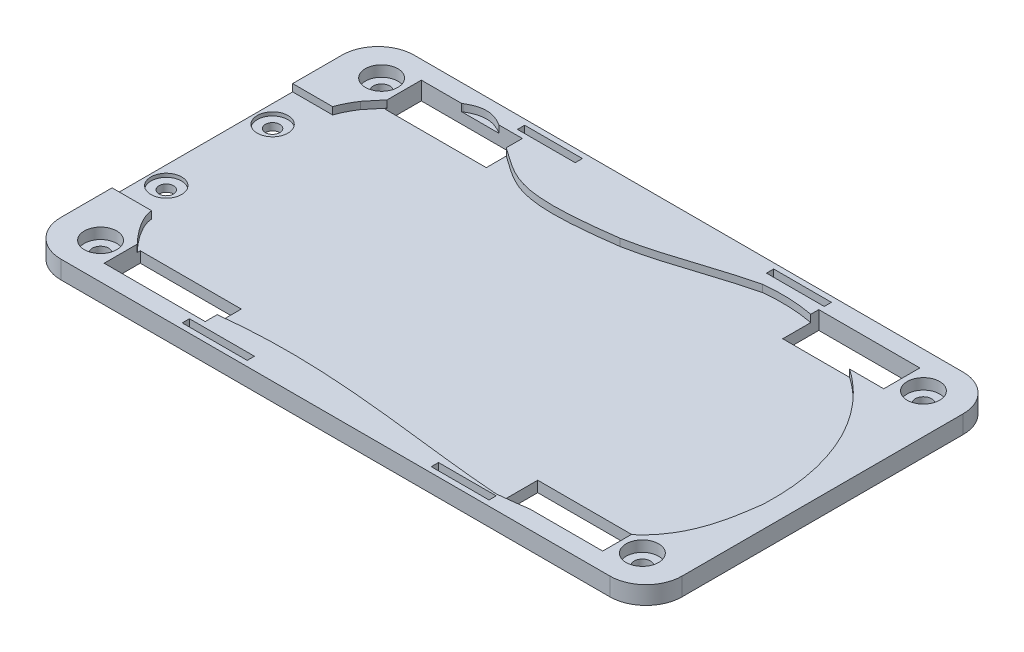
SolidWorks part; units mm, degrees
ref_plane "Front Plane" through (0, 0, 0) normal (0, 0, 1) x (1, 0, 0)
ref_plane "Top Plane" through (0, 0, 0) normal (0, 1, 0) x (1, 0, 0)
ref_plane "Right Plane" through (0, 0, 0) normal (1, 0, 0) x (0, 0, -1)
sketch "Sketch1" plane through (0, 0, 0) normal (0, 1, 0) x (1, 0, 0)
  line L1 (-78.1571, 35.933) -> (-78.1571, -14.1122)
  line L2 (78.9797, 0.0343) -> (-78.1571, 0.0343) construction
  line L3 (-77.1571, 35.7646) -> (-77.1571, -14.1122)
  line L4 (78.9797, -0.9657) -> (-78.1571, -0.9657)
  arc A1 (37.8695, -35.2975) -> (39.5975, -35.2134) centre (38.2635, -25.6055) ccw
  arc A2 (37.9263, -34.299) -> (39.4753, -34.2207) centre (38.2635, -25.6055) ccw
  spline S0 degree 1 poles (-77.1571, -14.1122) (-56.919, -31.9168) knots 0 0 1 1 construction
  spline S1 degree 1 poles (-56.919, -31.9168) (37.9263, -34.299) knots 0 0 1 1 construction
  spline S2 degree 1 poles (39.4753, -34.2207) (77.9849, 0.1477) knots 0 0 1 1 construction
  spline S3 degree 1 poles (77.9849, 0.1477) (25.0602, 52.8732) knots 0 0 1 1 construction
  spline S4 degree 1 poles (25.0602, 52.8732) (-5.6593, 44.1904) knots 0 0 1 1 construction
  spline S5 degree 1 poles (-5.6593, 44.1904) (-43.9853, 50.6886) knots 0 0 1 1 construction
  spline S6 degree 1 poles (-43.9853, 50.6886) (-59.7702, 54.7238) knots 0 0 1 1 construction
  spline S7 degree 1 poles (-59.7702, 54.7238) (-74.5158, 41.0521) knots 0 0 1 1 construction
  spline S8 degree 1 poles (-74.5158, 41.0521) (-77.1571, 35.7646) knots 0 0 1 1 construction
  spline S9 degree 3 poles (-77.1571, -14.1122) (-77.1565, -14.3701) (-77.1092, -14.8732) (-76.8359, -15.9559) (-76.1879, -17.5008) (-75.044, -19.4183) (-73.152, -22.0092) (-70.3495, -25.0822) (-66.8736, -28.0972) (-63.6864, -30.2141) (-61.0019, -31.4062) (-58.8274, -31.848) (-57.5718, -31.8794) (-56.919, -31.9168) knots 0.000484 0.000484 0.000484 0.000484 0.031521 0.062558 0.124632 0.186706 0.248781 0.372929 0.497077 0.621225 0.745373 0.869521 0.993669 0.993669 0.993669 0.993669
  spline S10 degree 3 poles (-56.919, -31.9168) (-56.6769, -31.8873) (-56.2021, -31.8274) (-55.1791, -31.687) (-53.8294, -31.4877) (-52.0759, -31.2184) (-49.5744, -30.8354) (-46.1465, -30.3372) (-41.5825, -29.7813) (-36.5976, -29.3261) (-29.4274, -28.913) (-19.5571, -28.8468) (-6.4839, -29.5875) (5.2448, -30.7865) (15.023, -31.9295) (22.521, -32.809) (30.1538, -33.642) (35.3408, -34.1075) (37.9263, -34.299) knots 0.000538 0.000538 0.000538 0.000538 0.016152 0.031766 0.062993 0.094221 0.125449 0.187904 0.250359 0.312815 0.37527 0.50018 0.625091 0.750001 0.812457 0.874912 0.937367 0.999822 0.999822 0.999822 0.999822
  spline S11 degree 3 poles (39.4753, -34.2207) (41.0079, -34.0574) (44.09, -33.7147) (50.0835, -32.8429) (57.0969, -31.1859) (64.2184, -27.8839) (69.7763, -23.1857) (73.0497, -18.2789) (74.9177, -14.0269) (75.9805, -10.7732) (76.7509, -7.5724) (77.1995, -5.064) (77.4798, -3.2279) (77.6607, -1.9649) (77.8261, -0.8108) (77.9301, -0.1834) (77.9849, 0.1477) knots -0.000309 -0.000309 -0.000309 -0.000309 0.063093 0.126495 0.253299 0.380104 0.506908 0.633712 0.697114 0.760516 0.823918 0.88732 0.919021 0.950722 0.982423 1.014124 1.014124 1.014124 1.014124
  spline S12 degree 3 poles (77.9849, 0.1477) (78.0286, 1.2633) (78.0637, 3.5224) (77.9426, 6.757) (77.6596, 9.9047) (77.0733, 13.9671) (75.9626, 18.7836) (73.4433, 25.9357) (69.0206, 33.8098) (62.0495, 41.4932) (53.7895, 47.3444) (44.6121, 51.2947) (34.9036, 53.2804) (28.3113, 53.2357) (25.0602, 52.8732) knots 0.000169 0.000169 0.000169 0.000169 0.031414 0.062658 0.093902 0.125147 0.187635 0.250124 0.375101 0.500079 0.625056 0.750034 0.875011 0.999988 0.999988 0.999988 0.999988
  spline S13 degree 3 poles (25.0602, 52.8732) (19.8954, 51.6294) (12.3224, 49.1317) (2.1607, 45.9713) (-3.0371, 44.6913) (-5.6593, 44.1904) knots 0.000659 0.000659 0.000659 0.000659 0.498067 0.746772 0.995476 0.995476 0.995476 0.995476
  spline S14 degree 3 poles (-5.6593, 44.1904) (-6.6879, 44.0461) (-8.7287, 43.7719) (-12.9633, 43.2668) (-18.1826, 42.7952) (-23.9015, 42.6322) (-28.8306, 42.9899) (-32.9666, 43.9514) (-35.9177, 45.2914) (-38.1959, 46.6779) (-39.9392, 47.8658) (-41.507, 48.9798) (-42.8638, 49.9292) (-43.6163, 50.4405) (-43.9853, 50.6886) knots -0.000196 -0.000196 -0.000196 -0.000196 0.062587 0.12537 0.250936 0.376501 0.502067 0.627632 0.753198 0.815981 0.878764 0.941546 0.972938 1.004329 1.004329 1.004329 1.004329
  spline S15 degree 3 poles (-43.9853, 50.6886) (-44.2445, 50.8673) (-44.7682, 51.2325) (-45.7507, 51.9331) (-46.8912, 52.7591) (-48.146, 53.6496) (-49.6971, 54.6811) (-51.4608, 55.6487) (-53.4077, 56.2593) (-55.2517, 56.3574) (-56.711, 56.0808) (-57.7948, 55.7138) (-58.5465, 55.3915) (-59.2299, 55.0428) (-59.5837, 54.8359) (-59.7702, 54.7238) knots -0.002497 -0.002497 -0.002497 -0.002497 0.029066 0.060629 0.123754 0.18688 0.250006 0.376257 0.502509 0.62876 0.755012 0.818137 0.881263 0.944389 1.007515 1.007515 1.007515 1.007515
  spline S16 degree 3 poles (-78.1571, -14.1122) (-78.1559, -14.7524) (-77.9173, -15.9777) (-77.0678, -17.9828) (-75.8538, -20.0098) (-73.8827, -22.6985) (-70.9901, -25.8584) (-67.4096, -28.9504) (-64.0991, -31.1349) (-61.2379, -32.3904) (-59.243, -32.7789) (-57.8421, -32.8756) (-57.2118, -32.9007) (-56.8882, -32.9203) knots 0.000409 0.000409 0.000409 0.000409 0.062843 0.125276 0.18771 0.250143 0.375011 0.499878 0.624745 0.749612 0.874479 0.936913 0.999346 0.999346 0.999346 0.999346
  spline S17 degree 3 poles (-56.8882, -32.9203) (-56.6427, -32.8908) (-56.1603, -32.8306) (-55.1309, -32.6904) (-53.7754, -32.491) (-52.0233, -32.2221) (-49.5292, -31.8398) (-46.1189, -31.3427) (-41.5829, -30.7872) (-36.6286, -30.3313) (-29.4997, -29.9158) (-19.6749, -29.8441) (-6.6369, -30.5782) (5.0856, -31.7749) (14.8757, -32.919) (22.3927, -33.8009) (30.0532, -34.6371) (35.2704, -35.1052) (37.8695, -35.2975) knots -0.001373 -0.001373 -0.001373 -0.001373 0.014273 0.029919 0.06121 0.092502 0.123794 0.186377 0.24896 0.311543 0.374127 0.499293 0.62446 0.749626 0.81221 0.874793 0.937376 0.99996 0.99996 0.99996 0.99996
  spline S18 degree 3 poles (39.5975, -35.2134) (41.1398, -35.049) (44.2356, -34.7045) (50.3018, -33.8209) (57.4502, -32.1301) (64.7991, -28.7164) (70.5782, -23.8111) (73.9656, -18.7006) (75.8832, -14.3057) (76.9672, -10.962) (77.7479, -7.6914) (78.1997, -5.145) (78.4804, -3.2966) (78.6613, -2.0308) (78.824, -0.9009) (78.9276, -0.2806) (78.9816, 0.0458) knots -0.000086 -0.000086 -0.000086 -0.000086 0.063428 0.126941 0.253967 0.380993 0.50802 0.635046 0.698559 0.762072 0.825585 0.889098 0.920855 0.952612 0.984368 1.016125 1.016125 1.016125 1.016125
  spline S19 degree 3 poles (78.9816, 0.0458) (79.0271, 1.1797) (79.0647, 3.4739) (78.9444, 6.7697) (78.6587, 9.9749) (78.0642, 14.1169) (76.9341, 19.0326) (74.3646, 26.3398) (69.8439, 34.3944) (62.712, 42.2543) (54.2626, 48.2351) (44.8799, 52.2671) (34.9529, 54.2886) (28.2109, 54.2351) (24.8869, 53.8601) knots -0.000407 -0.000407 -0.000407 -0.000407 0.03088 0.062166 0.093453 0.12474 0.187314 0.249888 0.375035 0.500183 0.62533 0.750478 0.875625 1.000773 1.000773 1.000773 1.000773
  spline S20 degree 3 poles (24.8869, 53.8601) (22.2839, 53.2349) (17.1223, 51.77) (6.9788, 48.4835) (-0.6206, 46.1711) (-5.8226, 45.1772) knots -0.001281 -0.001281 -0.001281 -0.001281 0.247714 0.49671 0.9947 0.9947 0.9947 0.9947
  spline S21 degree 3 poles (-5.8226, 45.1772) (-6.8463, 45.0337) (-8.8779, 44.761) (-13.0882, 44.2593) (-18.2643, 43.7927) (-23.9018, 43.6338) (-28.7026, 43.9859) (-32.6523, 44.9085) (-35.4477, 46.177) (-37.6484, 47.5152) (-39.3619, 48.6824) (-40.9248, 49.793) (-42.292, 50.7496) (-43.0505, 51.2651) (-43.4225, 51.5151) knots 0.000305 0.000305 0.000305 0.000305 0.063048 0.125791 0.251276 0.376761 0.502247 0.627732 0.753218 0.815961 0.878703 0.941446 0.972817 1.004189 1.004189 1.004189 1.004189
  spline S22 degree 3 poles (-43.4225, 51.5151) (-43.6786, 51.6918) (-44.1958, 52.0526) (-45.1684, 52.7462) (-46.308, 53.5714) (-47.577, 54.4721) (-49.1727, 55.5335) (-51.0441, 56.5648) (-53.2147, 57.2519) (-55.3195, 57.3652) (-56.9568, 57.0533) (-58.1477, 56.6506) (-58.9689, 56.2985) (-59.5708, 55.992) (-60.0059, 55.7483) (-60.1862, 55.6406) (-60.2803, 55.5839) knots -0.002294 -0.002294 -0.002294 -0.002294 0.029245 0.060783 0.12386 0.186936 0.250013 0.376167 0.50232 0.628473 0.754627 0.817704 0.88078 0.943857 0.975396 1.006934 1.006934 1.006934 1.006934
  spline S23 degree 3 poles (-60.2803, 55.5839) (-60.715, 55.3297) (-61.582, 54.801) (-63.2222, 53.7187) (-65.9105, 51.7373) (-69.2431, 48.741) (-72.0244, 45.6929) (-73.7392, 43.6279) (-74.6657, 42.4756) (-75.1049, 41.9202) (-75.3265, 41.639) knots 0.000427 0.000427 0.000427 0.000427 0.063268 0.126109 0.251792 0.503158 0.754524 0.880206 0.943048 1.005889 1.005889 1.005889 1.005889
  spline S24 degree 3 poles (-59.7702, 54.7238) (-60.1936, 54.4761) (-61.0386, 53.9612) (-62.6368, 52.9072) (-65.2587, 50.9763) (-68.5171, 48.0498) (-71.2443, 45.0657) (-73.1899, 42.7247) (-74.0698, 41.6179) (-74.5158, 41.0521) knots 0.000174 0.000174 0.000174 0.000174 0.062881 0.125589 0.251004 0.501833 0.752662 0.878077 1.003492 1.003492 1.003492 1.003492
  spline S25 degree 3 poles (-74.5158, 41.0521) (-75.0658, 40.2217) (-76.0765, 38.4779) (-76.8336, 36.6875) (-77.1571, 35.7646) knots 0.499549 0.499549 0.499549 0.499549 0.499766 0.499983 0.499983 0.499983 0.499983
  spline S26 degree 3 poles (-75.3265, 41.639) (-75.92, 40.746) (-77.0064, 38.8701) (-77.815, 36.9314) (-78.1571, 35.933) knots 0.499546 0.499546 0.499546 0.499546 0.49977 0.499995 0.499995 0.499995 0.499995
  point P0 (0.4631, 0.0343)
  dimension "D1" = 1
sketch "Sketch6" plane through (0, 0, 0) normal (0, 1, 0) x (1, 0, 0)
  line L0 (-78.1571, 35.933) -> (-78.1571, -14.1122) construction
  line L1 (73.9816, 59.5839) -> (-78.1571, 59.5839)
  line L2 (83.9816, 49.5839) -> (83.9816, -28.2975)
  line L3 (73.9816, -38.2975) -> (-78.1571, -38.2975)
  line L4 (-88.1571, 49.5839) -> (-88.1571, -28.2975)
  arc A0 (-78.1571, -38.2975) -> (-88.1571, -28.2975) centre (-78.1571, -28.2975) cw
  arc A1 (-88.1571, 49.5839) -> (-78.1571, 59.5839) centre (-78.1571, 49.5839) cw
  arc A2 (73.9816, 59.5839) -> (83.9816, 49.5839) centre (73.9816, 49.5839) cw
  arc A3 (83.9816, -28.2975) -> (73.9816, -38.2975) centre (73.9816, -28.2975) cw
  dimension "D5" = 10
  dimension "D1" = 5
  dimension "D2" = 10
  dimension "D3" = 3
  dimension "D4" = 4
extrude "Boss-Extrude2" add sketch "Sketch6" along normal blind 6.5
extrude "Cut-Extrude1" cut sketch "Sketch1" along normal blind 2.5 contours A2 S11 L4 L3 S9 S10 | S24 S25 L3 L4 S11 S12 S13 S14 S15 region at (0.1139, 0, 15.5782) region at (-2.2602, 0, -23.2786)
sketch "Sketch7" plane through (0, 0, 0) normal (0, -1, 0) x (1, 0, 0)
  line L1 (-76.2189, 14.1122) -> (-91.3452, 14.1122)
  line L2 (-76.2189, 14.1122) -> (-76.2189, -35.933)
  line L3 (-76.2189, -35.933) -> (-91.3452, -35.933)
  line L4 (-91.3452, 14.1122) -> (-91.3452, -35.933)
extrude "Cut-Extrude2" cut sketch "Sketch7" against normal up to surface (2.5 mm away) contours L2 L1 L4 L3 up to face at (-19.4492, 2.5, -12.7234)
sketch "Sketch8" plane through (0, 6.5, 0) normal (0, 1, 0) x (1, 0, 0)
  line L0 (83.9816, 10.6432) -> (-88.1571, 10.6432) construction
  line L1 (83.9816, -28.2975) -> (83.9816, 49.5839) construction
  line L2 (-88.1571, 49.5839) -> (-88.1571, -28.2975) construction
  line L3 (-2.0877, 59.5839) -> (-2.0877, -38.2975) construction
  line L4 (73.9816, 59.5839) -> (-78.1571, 59.5839) construction
  line L5 (-78.1571, -38.2975) -> (73.9816, -38.2975) construction
  line L7 (78.9816, 54.5839) -> (38.9816, 54.5839)
  line L8 (78.9816, 54.5839) -> (78.9816, 44.5839)
  line L9 (78.9816, 44.5839) -> (38.9816, 44.5839)
  line L10 (38.9816, 54.5839) -> (38.9816, 44.5839)
  line L22 (38.9816, 49.5839) -> (78.9816, 49.5839) construction
  line L23 (66.9816, 54.5839) -> (66.9816, 44.5839)
  circle A1 centre (72.9816, 49.5839) radius 3.5
  dimension "D6" = 7
  dimension "D1" = 10
  dimension "D2" = 40
  dimension "D3" = 5
  dimension "D4" = 5
  dimension "D5" = 6
  dimension "D7" = 6
sketch "Sketch9" plane through (0, 0, 0) normal (0, -1, 0) x (1, 0, 0)
  circle A0 centre (72.9816, -49.5839) radius 4.5
  dimension "D1" = 9
extrude "Cut-Extrude5" cut sketch "Sketch9" against normal blind 3.5
sketch "Sketch10" plane through (0, 3.5, 0) normal (0, -1, 0) x (1, 0, 0)
  circle A0 centre (72.9816, -49.5839) radius 2.25
  dimension "D1" = 4.5
extrude "Cut-Extrude6" cut sketch "Sketch10" against normal blind 21
extrude "Cut-Extrude8" cut sketch "Sketch8" against normal blind 42 contours L23 L7 L10 L9 region at (52.9816, 6.5, -49.5839)
extrude "Cut-Extrude9" cut sketch "Sketch8<3>" against normal blind 1 contours L7 L23 L9 L8 A1 region at (78.8254, 6.5, -49.5839)
sketch "Sketch8<3>" plane through (0, 6.5, 0) normal (0, 1, 0) x (1, 0, 0) same geometry as "Sketch8"
sketch "Sketch12" plane through (0, 6.5, 0) normal (0, 1, 0) x (1, 0, 0)
  line L0 (-88.1571, 10.6432) -> (83.9816, 10.6432) construction
  line L1 (-88.1571, 49.5839) -> (-88.1571, -28.2975) construction
  line L2 (83.9816, -28.2975) -> (83.9816, 49.5839) construction
  line L3 (-2.0877, 59.5839) -> (-2.0877, -36.8461) construction
  line L4 (73.9816, 59.5839) -> (-78.1571, 59.5839) construction
ref_plane "Plane1" through (0, 0, -10.6432) normal (0, 0, 1) x (1, 0, 0)
ref_plane "Plane2" through (-2.0877, 0, 0) normal (-1, 0, 0) x (0, 0, 1)
mirror "Mirror1" about plane through (0, 0, -10.6432) normal (0, 0, 1) of "Cut-Extrude5", "Cut-Extrude6", "Cut-Extrude8", "Cut-Extrude9"
mirror "Mirror2" about plane through (-2.0877, 0, 0) normal (-1, 0, 0) of "Mirror1", "Cut-Extrude9", "Cut-Extrude8", "Cut-Extrude6", "Cut-Extrude5"
sketch "Sketch13" plane through (0, 6.5, 0) normal (0, 1, 0) x (1, 0, 0)
  line L0 (-83.1571, 44.5839) -> (-43.1571, 44.5839) construction
  line L1 (58.9816, 39.5839) -> (-63.1571, 39.5839)
  line L2 (58.9816, 39.5839) -> (58.9816, -18.2975)
  line L3 (58.9816, -18.2975) -> (-63.1571, -18.2975)
  line L4 (-63.1571, 39.5839) -> (-63.1571, -18.2975)
  line L5 (58.9816, 39.5839) -> (-63.1571, -18.2975) construction
  line L6 (58.9816, -18.2975) -> (-63.1571, 39.5839) construction
  line L7 (-83.1571, -23.2975) -> (-43.1571, -23.2975) construction
  line L8 (83.9816, -28.2975) -> (83.9816, 49.5839) construction
  line L9 (-88.1571, 49.5839) -> (-88.1571, -28.2975) construction
  point P0 (-2.0877, 10.6432)
  dimension "D1" = 5
  dimension "D2" = 5
  dimension "D3" = 25
  dimension "D4" = 25
extrude "Cut-Extrude10" cut sketch "Sketch13" against normal blind 1
sketch "Sketch14" plane through (0, 5.5, 0) normal (0, 1, 0) x (1, 0, 0)
  line L0 (-63.1571, 10.6432) -> (58.9816, 10.6432) construction
  line L1 (-63.1571, 39.5839) -> (-63.1571, -18.2975) construction
  line L2 (58.9816, -18.2975) -> (58.9816, 39.5839) construction
  line L3 (-63.1571, -9.3568) -> (58.9816, -9.3568) construction
  line L4 (-63.1571, 10.6432) -> (58.9816, 10.6432) construction
  line L5 (-63.1571, 30.6432) -> (58.9816, 30.6432) construction
  circle A1 centre (-12.0877, 10.6432) radius 2.5
  circle A2 centre (-32.0877, 10.6432) radius 2.5
  circle A3 centre (-52.0877, 10.6432) radius 2.5
  circle A4 centre (-12.0877, 10.6432) radius 2.5
  circle A5 centre (-32.0877, 10.6432) radius 2.5
  circle A6 centre (7.9123, 10.6432) radius 2.5
  circle A7 centre (-12.0877, 10.6432) radius 2.5
  circle A8 centre (27.9123, 10.6432) radius 2.5
  circle A9 centre (7.9123, 10.6432) radius 2.5
  circle A10 centre (7.9123, 10.6432) radius 2.5
  circle A11 centre (27.9123, 10.6432) radius 2.5
  circle A12 centre (47.9123, 10.6432) radius 2.5
  circle A13 centre (-12.0877, -9.3568) radius 2.5
  circle A14 centre (-32.0877, -9.3568) radius 2.5
  circle A15 centre (-52.0877, -9.3568) radius 2.5
  circle A16 centre (-12.0877, -9.3568) radius 2.5
  circle A17 centre (-32.0877, -9.3568) radius 2.5
  circle A18 centre (7.9123, -9.3568) radius 2.5
  circle A19 centre (-12.0877, -9.3568) radius 2.5
  circle A20 centre (27.9123, -9.3568) radius 2.5
  circle A21 centre (7.9123, -9.3568) radius 2.5
  circle A22 centre (7.9123, -9.3568) radius 2.5
  circle A23 centre (27.9123, -9.3568) radius 2.5
  circle A24 centre (47.9123, -9.3568) radius 2.5
  circle A25 centre (-12.0877, 10.6432) radius 2.5
  circle A26 centre (-32.0877, 10.6432) radius 2.5
  circle A27 centre (-52.0877, 10.6432) radius 2.5
  circle A28 centre (-12.0877, 10.6432) radius 2.5
  circle A29 centre (-32.0877, 10.6432) radius 2.5
  circle A30 centre (7.9123, 10.6432) radius 2.5
  circle A31 centre (-12.0877, 10.6432) radius 2.5
  circle A32 centre (27.9123, 10.6432) radius 2.5
  circle A33 centre (7.9123, 10.6432) radius 2.5
  circle A34 centre (7.9123, 10.6432) radius 2.5
  circle A35 centre (27.9123, 10.6432) radius 2.5
  circle A36 centre (47.9123, 10.6432) radius 2.5
  circle A37 centre (-12.0877, 30.6432) radius 2.5
  circle A38 centre (-32.0877, 30.6432) radius 2.5
  circle A39 centre (-52.0877, 30.6432) radius 2.5
  circle A40 centre (-12.0877, 30.6432) radius 2.5
  circle A41 centre (-32.0877, 30.6432) radius 2.5
  circle A42 centre (7.9123, 30.6432) radius 2.5
  circle A43 centre (-12.0877, 30.6432) radius 2.5
  circle A44 centre (27.9123, 30.6432) radius 2.5
  circle A45 centre (7.9123, 30.6432) radius 2.5
  circle A46 centre (7.9123, 30.6432) radius 2.5
  circle A47 centre (27.9123, 30.6432) radius 2.5
  circle A48 centre (47.9123, 30.6432) radius 2.5
  point P8 (-2.0877, 10.6432)
  point P37 (-2.0877, -9.3568)
  point P64 (-2.0877, 10.6432)
  point P91 (-2.0877, 30.6432)
  dimension "D2" = 5
  dimension "D1" = 10
  dimension "D3" = 3
  dimension "D4" = 4
  dimension "D5" = 2
  dimension "D6" = 2
extrude "Cut-Extrude11" cut sketch "Sketch14" against normal blind 57 contours A39 | A42 | A44 | A48 | A12 | A6 | A1 | A2 | A3 | A24 | A20 | A18 | A13 | A14 | A15 | A38 | A37 | A8 region at (-12.0877, 5.5, -10.6432) region at (-32.0877, 5.5, -10.6432) region at (-52.0877, 5.5, -10.6432) region at (7.9123, 5.5, -10.6432) region at (47.9123, 5.5, -10.6432) region at (-12.0877, 5.5, 9.3568) region at (-32.0877, 5.5, 9.3568) region at (-52.0877, 5.5, 9.3568) region at (7.9123, 5.5, 9.3568) region at (27.9123, 5.5, 9.3568) region at (47.9123, 5.5, 9.3568) region at (-52.0877, 5.5, -30.6432) region at (7.9123, 5.5, -30.6432) region at (27.9123, 5.5, -30.6432) region at (47.9123, 5.5, -30.6432)
sketch "Sketch16" plane through (0, 0, 0) normal (0, -1, 0) x (1, 0, 0)
  line L0 (78.9816, -0.5458) -> (78.9816, -79.1994) construction
  line L1 (22.9816, -56.0839) -> (-37.6427, -56.0839) construction
  line L2 (73.9816, -59.5839) -> (-78.1571, -59.5839) construction
  line L3 (38.9816, -54.3238) -> (38.9816, 38.2975) construction
  line L4 (38.9816, -59.5839) -> (38.9816, -54.3238) construction
  line L5 (38.9816, -56.0839) -> (22.9816, -56.0839)
  line L6 (38.9816, -56.0839) -> (38.9816, -58.0839)
  line L7 (38.9816, -58.0839) -> (22.9816, -58.0839)
  line L8 (22.9816, -56.0839) -> (22.9816, -58.0839)
  line L9 (-78.1571, 38.2975) -> (73.9816, 38.2975) construction
  line L10 (22.9816, -56.0839) -> (22.9816, 38.2975) construction
  line L12 (38.9816, 36.7975) -> (22.9816, 36.7975)
  line L13 (38.9816, 36.7975) -> (38.9816, 34.7975)
  line L14 (38.9816, 34.7975) -> (22.9816, 34.7975)
  line L15 (22.9816, 36.7975) -> (22.9816, 34.7975)
  line L16 (22.9816, 34.7975) -> (-46.0184, 34.7975) construction
  line L17 (-30.0184, -56.0839) -> (-46.0184, -56.0839)
  line L18 (-30.0184, -56.0839) -> (-30.0184, -58.0839)
  line L19 (-30.0184, -58.0839) -> (-46.0184, -58.0839)
  line L20 (-46.0184, -56.0839) -> (-46.0184, -58.0839)
  line L22 (-28.0184, 34.7975) -> (-46.0184, 34.7975)
  line L23 (-28.0184, 34.7975) -> (-28.0184, 36.7975)
  line L24 (-28.0184, 36.7975) -> (-46.0184, 36.7975)
  line L25 (-46.0184, 34.7975) -> (-46.0184, 36.7975)
  dimension "D1" = 40
  dimension "D2" = 16
  dimension "D3" = 1.5
  dimension "D4" = 2
  dimension "D5" = 2
  dimension "D6" = 1.5
  dimension "D7" = 125
  dimension "D8" = 16
  dimension "D9" = 2
  dimension "D10" = 18
  dimension "D11" = 2
extrude "Cut-Extrude12" cut sketch "Sketch16" against normal blind 57
sketch "Sketch17" plane through (0, 5.5, 0) normal (0, 1, 0) x (1, 0, 0)
  line L1 (-99.5963, 69.0247) -> (98.4238, 69.0247)
  line L2 (-99.5963, 69.0247) -> (-99.5963, -53.2143)
  line L3 (-99.5963, -53.2143) -> (98.4238, -53.2143)
  line L4 (98.4238, 69.0247) -> (98.4238, -53.2143)
extrude "Cut-Extrude14" cut sketch "Sketch17" along normal blind 48.5
sketch "Sketch23" plane through (0, 2.5, 0) normal (0, -1, 0) x (1, 0, 0)
  line L0 (-88.1571, -10.9104) -> (-64.7808, -10.9104) construction
  line L1 (-88.1571, -35.933) -> (-88.1571, 14.1122) construction
  circle A0 centre (-83.1571, 4.0896) radius 2
  circle A1 centre (-83.1571, 4.0896) radius 4.25
  dimension "D1" = 4
  dimension "D4" = 8.5
  dimension "D2" = 15
  dimension "D3" = 5
extrude "Cut-Extrude15" cut sketch "Sketch23" against normal blind 48.5 contours A0
extrude "Cut-Extrude16" cut sketch "Sketch23<3>" against normal blind 1
sketch "Sketch23<3>" plane through (0, 2.5, 0) normal (0, -1, 0) x (1, 0, 0) same geometry as "Sketch23"
mirror "Mirror4" about plane through (0, 0, -10.6432) normal (0, 0, 1) of "Cut-Extrude16", "Cut-Extrude15"
sketch "Sketch24" plane through (0, 5.5, 0) normal (0, 1, 0) x (1, 0, 0)
  circle A0 centre (-77.1571, 49.5839) radius 3.25
  circle A1 centre (-77.1571, 49.5839) radius 2.25
  circle A2 centre (72.9816, 49.5839) radius 2.25
  circle A3 centre (72.9816, 49.5839) radius 3.25
  circle A4 centre (72.9816, -28.2975) radius 2.25
  circle A5 centre (-77.1571, -28.2975) radius 2.25
  circle A6 centre (-77.1571, -28.2975) radius 3.25
  circle A7 centre (72.9816, -28.2975) radius 3.25
  dimension "D1" = 6.5
  dimension "D2" = 6.5
  dimension "D3" = 6.5
  dimension "D4" = 6.5
extrude "Boss-Extrude3" add sketch "Sketch24" along normal blind 3
ref_plane "Plane3" through (0, 0, 0) normal (0, -1, 0) x (-1, 0, 0)
mirror "Mirror5" about plane through (0, 0, 0) normal (0, -1, 0) of "Boss-Extrude3", "Mirror4", "Cut-Extrude16", "Cut-Extrude15", "Cut-Extrude14", "Cut-Extrude12", "Cut-Extrude10", "Mirror2", "Mirror1", "Cut-Extrude9", "Cut-Extrude8", "Cut-Extrude6", "Cut-Extrude5", "Cut-Extrude2", "Cut-Extrude1", "Boss-Extrude2", "Cut-Extrude11"
sketch "Sketch25" plane through (0, 5.5, 0) normal (0, 1, 0) x (1, 0, 0)
  line L1 (-109.2871, 73.7066) -> (111.0455, 73.7066)
  line L2 (-109.2871, 73.7066) -> (-109.2871, -75.7235)
  line L3 (-109.2871, -75.7235) -> (111.0455, -75.7235)
  line L4 (111.0455, 73.7066) -> (111.0455, -75.7235)
extrude "Cut-Extrude18" cut sketch "Sketch25" against normal up to surface (5.5 mm away) and the other way blind 10 contours L2 L1 L4 L3 up to plane "Plane3"
ref_plane "Plane4" through (-77.0974, 0, 0) normal (-1, 0, 0) x (0, 0, 1)
ref_plane "Plane6" through (0, 0, -35.933) normal (0, 0, 1) x (1, 0, 0)
sketch "Sketch26" plane through (0, 0, 0) normal (0, 1, 0) x (1, 0, 0)
  line L1 (-104.6518, 69.0589) -> (106.0904, 69.0589)
  line L2 (-104.6518, 69.0589) -> (-104.6518, -52.1551)
  line L3 (-104.6518, -52.1551) -> (106.0904, -52.1551)
  line L4 (106.0904, 69.0589) -> (106.0904, -52.1551)
extrude "Cut-Extrude19" cut sketch "Sketch26" against normal blind 0.5
sketch "Sketch27" plane through (0, -2.5, 0) normal (0, 1, 0) x (1, 0, 0)
  line L1 (-59.9586, 37.3138) -> (59.6605, 37.3138)
  line L2 (-59.9586, 37.3138) -> (-59.9586, -15.8502)
  line L3 (-59.9586, -15.8502) -> (59.6605, -15.8502)
  line L4 (59.6605, 37.3138) -> (59.6605, -15.8502)
extrude "Boss-Extrude4" add sketch "Sketch27" against normal up to surface (3 mm away) up to face at (72.9816, -5.5, 25.0475)
sketch "Sketch28" plane through (0, -2.5, 0) normal (0, 1, 0) x (1, 0, 0)
  line L0 (73.9816, 59.5839) -> (-78.1571, 59.5839) construction
  line L6 (-88.1571, -14.1122) -> (-88.1571, 35.933) construction
  point P0 (-26.0571, 3.8839)
  dimension "D1" = 55.7
  dimension "D2" = 62.1
